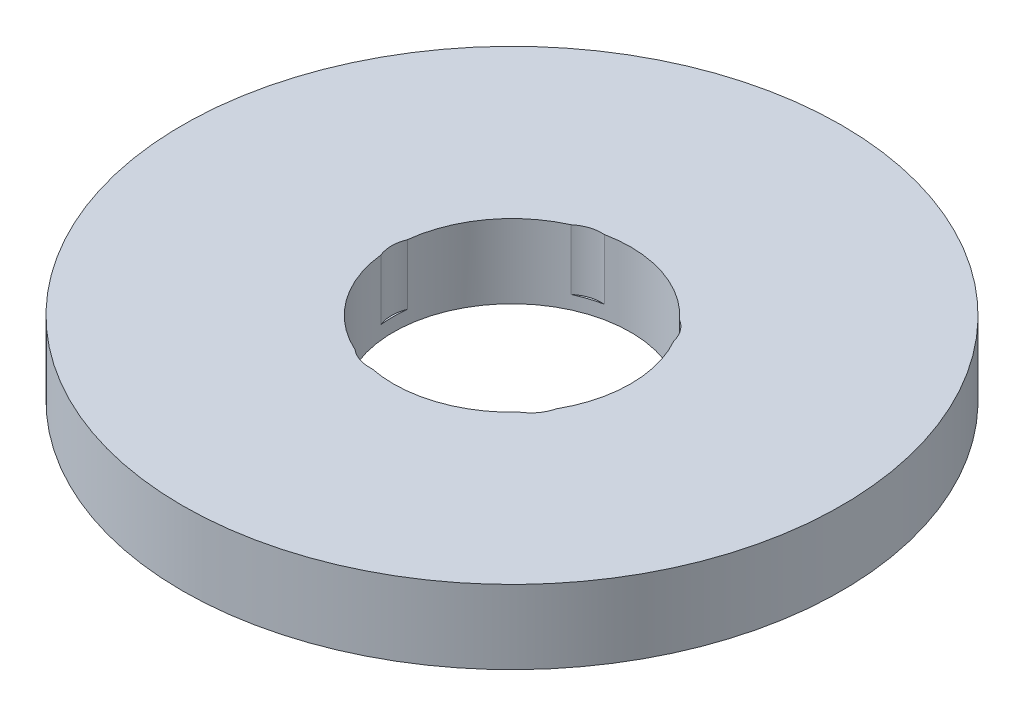
SolidWorks part; units mm, degrees
ref_plane "Front Plane" through (0, 0, 0) normal (0, 0, 1) x (1, 0, 0)
ref_plane "Top Plane" through (0, 0, 0) normal (0, 1, 0) x (1, 0, 0)
ref_plane "Right Plane" through (0, 0, 0) normal (1, 0, 0) x (0, 0, -1)
sketch "Sketch1" plane through (0, 0, 0) normal (0, 1, 0) x (1, 0, 0)
  circle A0 centre (0, 0) radius 62.5
  dimension "FLANGE_OD" = 125
extrude "Boss-Extrude1" add sketch "Sketch1" along normal blind 14
sketch "Sketch2" plane through (0, 0, 0) normal (0, 1, 0) x (1, 0, 0)
  circle A0 centre (0, 0) radius 22.5
  dimension "BORE_D" = 45
extrude "Cut-Extrude1" cut sketch "Sketch2" along normal through all
sketch "Sketch3" plane through (0, 14, 0) normal (0, 1, 0) x (1, 0, 0)
  circle A0 centre (0, 0) radius 16.2102 construction
  circle A1 centre (-16.2102, 0) radius 6.6402
  dimension "BOLT_D" = 13.2804
  dimension "BOLT_PCD" = 32.4203
extrude "Cut-Extrude2" cut sketch "Sketch3" against normal blind 11.448
pattern_circular "CirPattern1" count 5 over 360 about axis through (0, 0, 0) along (0, 1, 0) of "Cut-Extrude2"
